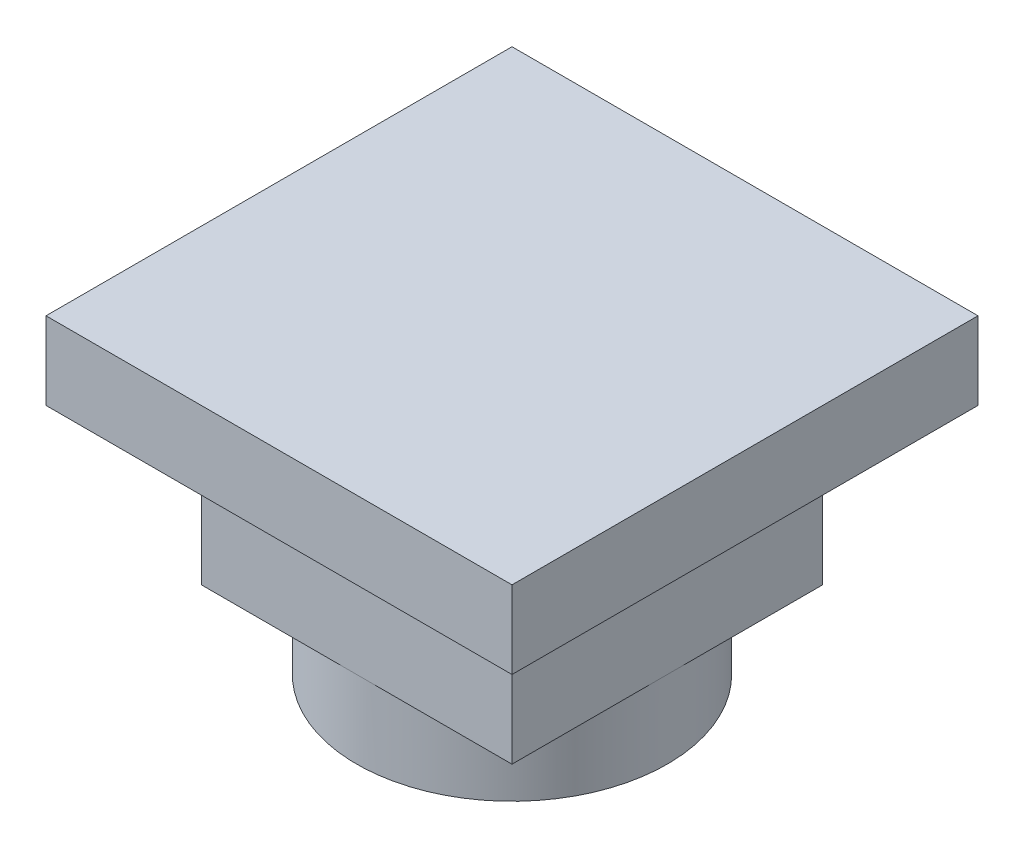
SolidWorks part; units mm, degrees
ref_plane "Front Plane" through (0, 0, 0) normal (0, 0, 1) x (1, 0, 0)
ref_plane "Top Plane" through (0, 0, 0) normal (0, 1, 0) x (1, 0, 0)
ref_plane "Right Plane" through (0, 0, 0) normal (1, 0, 0) x (0, 0, -1)
sketch "Sketch1" plane through (0, 0, 0) normal (0, 1, 0) x (1, 0, 0)
  line L1 (-0.5, -0.5) -> (0.5, -0.5)
  line L2 (-0.5, -0.5) -> (-0.5, 0.5)
  line L3 (-0.5, 0.5) -> (0.5, 0.5)
  line L4 (0.5, -0.5) -> (0.5, 0.5)
  line L5 (-0.5, -0.5) -> (0.5, 0.5) construction
  line L6 (-0.5, 0.5) -> (0.5, -0.5) construction
  point P0 (0, 0)
  dimension "D1" = 1
  dimension "D2" = 1
extrude "Boss-Extrude1" add sketch "Sketch1" along normal blind 0.5
sketch "Sketch2" plane through (0, 0.5, 0) normal (0, 1, 0) x (1, 0, 0)
  line L1 (-0.75, -0.75) -> (0.75, -0.75)
  line L2 (-0.75, -0.75) -> (-0.75, 0.75)
  line L3 (-0.75, 0.75) -> (0.75, 0.75)
  line L4 (0.75, -0.75) -> (0.75, 0.75)
  line L5 (-0.75, -0.75) -> (0.75, 0.75) construction
  line L6 (-0.75, 0.75) -> (0.75, -0.75) construction
  point P0 (0, 0)
  dimension "D1" = 1.5
  dimension "D2" = 1.5
extrude "Boss-Extrude2" add sketch "Sketch2" along normal blind 0.25
sketch "Sketch3" plane through (0, 0, 0) normal (0, -1, 0) x (1, 0, 0)
  circle A0 centre (0, 0) radius 0.5
  dimension "D1" = 1
extrude "Boss-Extrude3" add sketch "Sketch3" along normal blind 0.25
